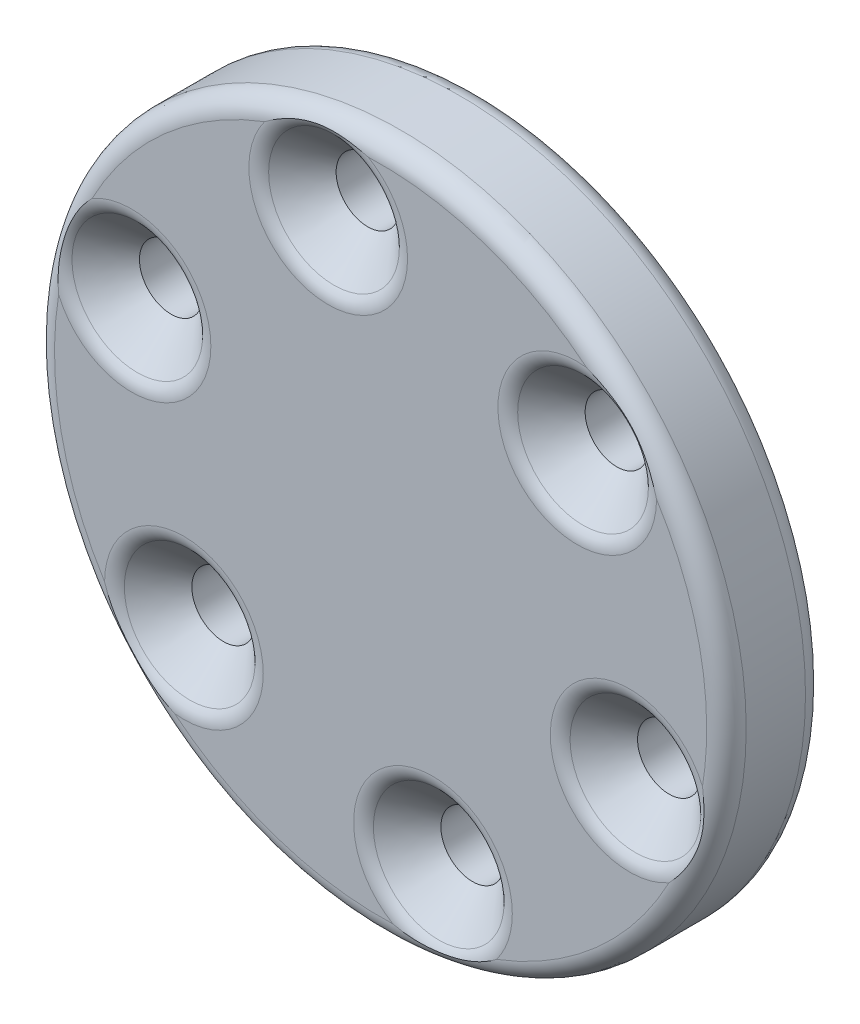
SolidWorks part; units mm, degrees
ref_plane "Plan de face" through (0, 0, 0) normal (0, 0, 1) x (1, 0, 0)
ref_plane "Plan de dessus" through (0, 0, 0) normal (0, 1, 0) x (1, 0, 0)
ref_plane "Plan de droite" through (0, 0, 0) normal (1, 0, 0) x (0, 0, -1)
sketch "Esquisse1" plane through (0, 0, 0) normal (0, 0, 1) x (1, 0, 0)
  circle A0 centre (0, 0) radius 17.5
  circle A1 centre (-2.6502, 13.0206) radius 1.6
  circle A2 centre (9.9511, 8.8054) radius 1.6
  circle A3 centre (12.6012, -4.2152) radius 1.6
  circle A4 centre (2.6502, -13.0206) radius 1.6
  circle A5 centre (-9.9511, -8.8054) radius 1.6
  circle A6 centre (-12.6012, 4.2152) radius 1.6
  point P55 (0, 0)
  dimension "D1" = 35
  dimension "D5" = 3.2
  dimension "D8" = 6
extrude "Boss.-Extru.1" add sketch "Esquisse1" along normal blind 5
chamfer "Chanfrein1" distance 2 angle 45 6 edges at (-1.0502, 13.0206, 5) (11.5511, 8.8054, 5) (14.2012, -4.2152, 5) (4.2502, -13.0206, 5) (-8.3511, -8.8054, 5) (-11.0012, 4.2152, 5)
fillet "Congé2" radius 1 14 edges at (17.5, 0, 5) (17.5, 0, 0) (-1.0502, 13.0206, 0) (11.5511, 8.8054, 0) (14.2012, -4.2152, 0) (4.2502, -13.0206, 0) (-8.3511, -8.8054, 0) (-11.0012, 4.2152, 0) (-9.0012, 4.2152, 5) (-6.3511, -8.8054, 5) (6.2502, -13.0206, 5) (16.2012, -4.2152, 5) (13.5511, 8.8054, 5) (0.9498, 13.0206, 5)
